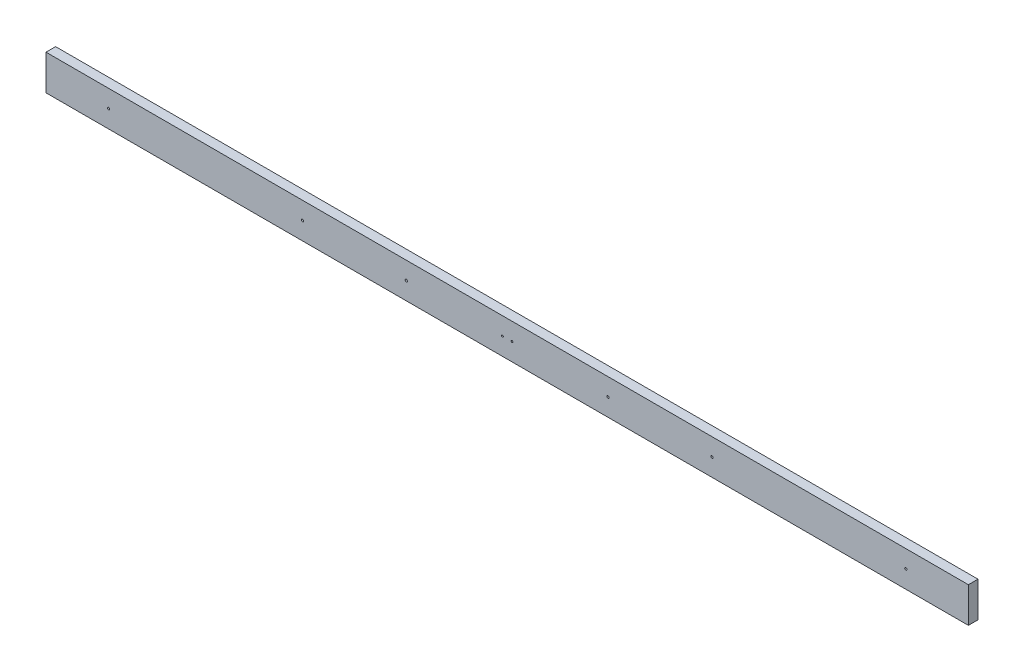
SolidWorks part; units mm, degrees
ref_plane "Front Plane" through (0, 0, 0) normal (0, 0, 1) x (1, 0, 0)
ref_plane "Top Plane" through (0, 0, 0) normal (0, 1, 0) x (1, 0, 0)
ref_plane "Right Plane" through (0, 0, 0) normal (1, 0, 0) x (0, 0, -1)
sketch "Sketch1" plane through (0, 0, 0) normal (0, 0, 1) x (1, 0, 0)
  line L1 (-1828.8, -69.85) -> (1828.8, -69.85)
  line L2 (-1828.8, -69.85) -> (-1828.8, 69.85)
  line L3 (-1828.8, 69.85) -> (1828.8, 69.85)
  line L4 (1828.8, -69.85) -> (1828.8, 69.85)
  line L5 (-1828.8, -69.85) -> (1828.8, 69.85) construction
  line L6 (-1828.8, 69.85) -> (1828.8, -69.85) construction
  point P0 (0, 0)
  dimension "D1" = 3657.6
  dimension "D2" = 139.7
extrude "Boss-Extrude1" add sketch "Sketch1" along normal blind 38.1
sketch "Sketch3" plane through (0, 0, 38.1) normal (0, 0, 1) x (1, 0, 0)
  line L0 (0, -69.85) -> (0, 69.85) construction
  line L1 (-1828.8, -69.85) -> (1828.8, -69.85) construction
  line L2 (1828.8, 69.85) -> (-1828.8, 69.85) construction
  line L3 (-25.4, -7.9375) -> (25.4, -7.9375) construction
  line L4 (-25.4, -7.9375) -> (-25.4, 7.9375) construction
  line L5 (-25.4, 7.9375) -> (25.4, 7.9375) construction
  line L6 (25.4, -7.9375) -> (25.4, 7.9375) construction
  line L7 (-19.05, 0) -> (19.05, 0) construction
  circle A0 centre (-19.05, 0) radius 3.5719
  circle A1 centre (19.05, 0) radius 3.5719
  point P14 (-25.4, 0)
  dimension "D8" = 7.1437
  dimension "D9" = 7.1437
  dimension "D1" = 15.875
  dimension "D2" = 7.9375
  dimension "D3" = 38.1
  dimension "D4" = 6.35
  dimension "D5" = 50.8
  dimension "D10" = 7.9375
extrude "Cut-Extrude2" cut sketch "Sketch3" against normal through all contours A0 | A1
sketch "Sketch4" plane through (0, 0, 38.1) normal (0, 0, 1) x (1, 0, 0)
  line L0 (0, 589.6071) -> (0, -768.8477)
  line L1 (762, 589.6071) -> (762, -768.8477)
  dimension "D1" = 762
sketch "Sketch5" plane through (0, 0, 38.1) normal (0, 0, 1) x (1, 0, 0)
  line L0 (-400, 0) -> (400, 0) construction
  circle A0 centre (400, 0) radius 4.4996
  circle A1 centre (-400, 0) radius 4.4996
  point P4 (0, 0)
  dimension "D2" = 8.9992
  dimension "D3" = 8.9992
  dimension "D1" = 800
extrude "Cut-Extrude3" cut sketch "Sketch5" against normal through all
sketch "Sketch6" plane through (0, 0, 38.1) normal (0, 0, 1) x (1, 0, 0)
  line L0 (1828.8, 0) -> (-1828.8, 0) construction
  line L1 (1828.8, -69.85) -> (1828.8, 69.85) construction
  line L2 (-1828.8, 69.85) -> (-1828.8, -69.85) construction
  line L3 (0, 69.85) -> (0, -69.85) construction
  line L4 (1828.8, 69.85) -> (-1828.8, 69.85) construction
  line L6 (-789.94, -403.86) -> (789.94, -403.86) construction
  line L7 (-789.94, -403.86) -> (-789.94, 403.86) construction
  line L8 (-789.94, 403.86) -> (789.94, 403.86) construction
  line L9 (789.94, -403.86) -> (789.94, 403.86) construction
  line L10 (-789.94, -403.86) -> (789.94, 403.86) construction
  line L11 (-789.94, 403.86) -> (789.94, -403.86) construction
  circle A0 centre (811.94, 0) radius 4.4996
  circle A1 centre (1580.6608, 0) radius 4.4996
  circle A3 centre (-1580.6608, 0) radius 4.4996
  circle A4 centre (-811.94, 0) radius 4.4996
  point P15 (400, 0)
  point P21 (0, 0)
  dimension "D2" = 8.9992
  dimension "D3" = 8.9992
  dimension "D1" = 768.7208
  dimension "D4" = 1579.88
  dimension "D5" = 807.72
  dimension "D6" = 22
extrude "Cut-Extrude4" cut sketch "Sketch6" against normal through all
sketch "Sketch7" plane through (0, 0, 38.1) normal (0, 0, 1) x (1, 0, 0)
  point P0 (-811.94, 0)
  point P1 (-1580.6608, 0)
  point P3 (400, 0)
  point P5 (811.94, 0)
  point P7 (1580.6608, 0)
